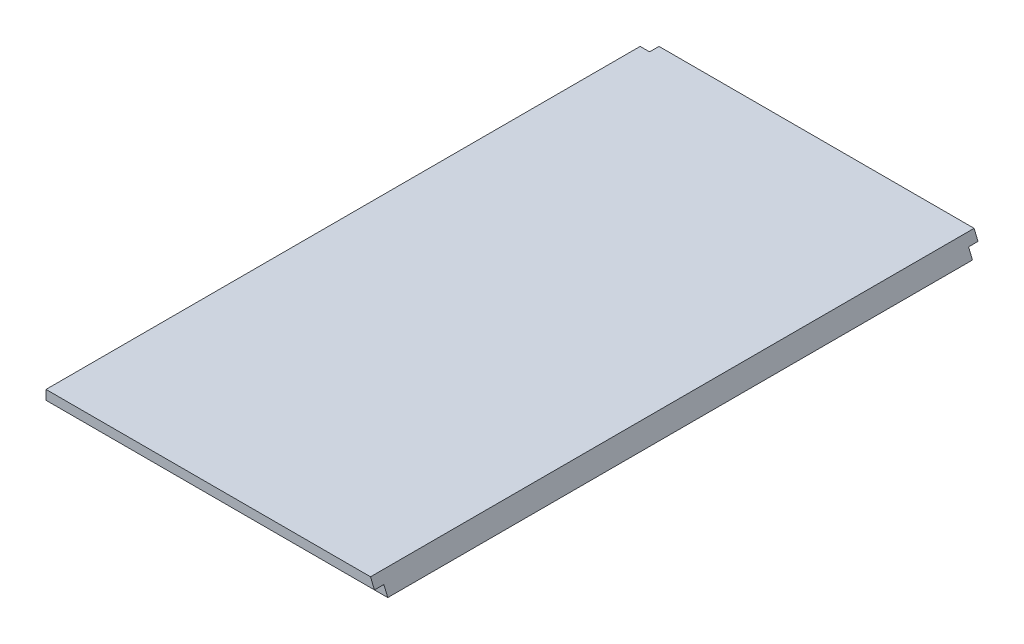
SolidWorks part; units mm, degrees
ref_plane "Front Plane" through (0, 0, 0) normal (0, 0, 1) x (1, 0, 0)
ref_plane "Top Plane" through (0, 0, 0) normal (0, 1, 0) x (1, 0, 0)
ref_plane "Right Plane" through (0, 0, 0) normal (1, 0, 0) x (0, 0, -1)
sketch "Sketch1" plane through (0, 0, 0) normal (0, 0, 1) x (1, 0, 0)
  line L0 (0, 0) -> (0, 12.7)
  line L1 (0, 12.7) -> (218.5135, 12.7)
  line L2 (218.5135, 12.7) -> (223.774, 0)
  line L3 (223.774, 0) -> (0, 0)
  dimension "D1" = 12.7
  dimension "D2" = 223.774
  dimension "D3" = 67.5
extrude "Boss-Extrude1" add sketch "Sketch1" along normal blind 406.4
sketch "Sketch2" plane through (0, 0, 0) normal (0, -1, 0) x (1, 0, 0)
  line L5 (223.774, 406.4) -> (223.774, 0) construction
  line L6 (0, 406.4) -> (223.774, 406.4)
  line L7 (0, 406.4) -> (0, 400.05)
  line L8 (0, 400.05) -> (223.774, 400.05)
  line L9 (223.774, 406.4) -> (223.774, 400.05)
  line L10 (0, 0) -> (223.774, 0) construction
  line L11 (6.35, 0) -> (223.774, 0)
  line L12 (6.35, 0) -> (6.35, 6.35)
  line L13 (6.35, 6.35) -> (223.774, 6.35)
  line L14 (223.774, 0) -> (223.774, 6.35)
  line L15 (0, 406.4) -> (0, 0) construction
  dimension "D1" = 6.35
  dimension "D2" = 6.35
  dimension "D3" = 6.35
extrude "Cut-Extrude1" cut sketch "Sketch2" against normal blind 6.35
sketch "Sketch3" plane through (0, 0, 0) normal (0, -1, 0) x (1, 0, 0)
  line L1 (6.35, 6.35) -> (0, 6.35)
  line L2 (6.35, 6.35) -> (6.35, 0)
  line L3 (6.35, 0) -> (0, 0)
  line L4 (0, 6.35) -> (0, 0)
extrude "Cut-Extrude2" cut sketch "Sketch3" against normal through all
